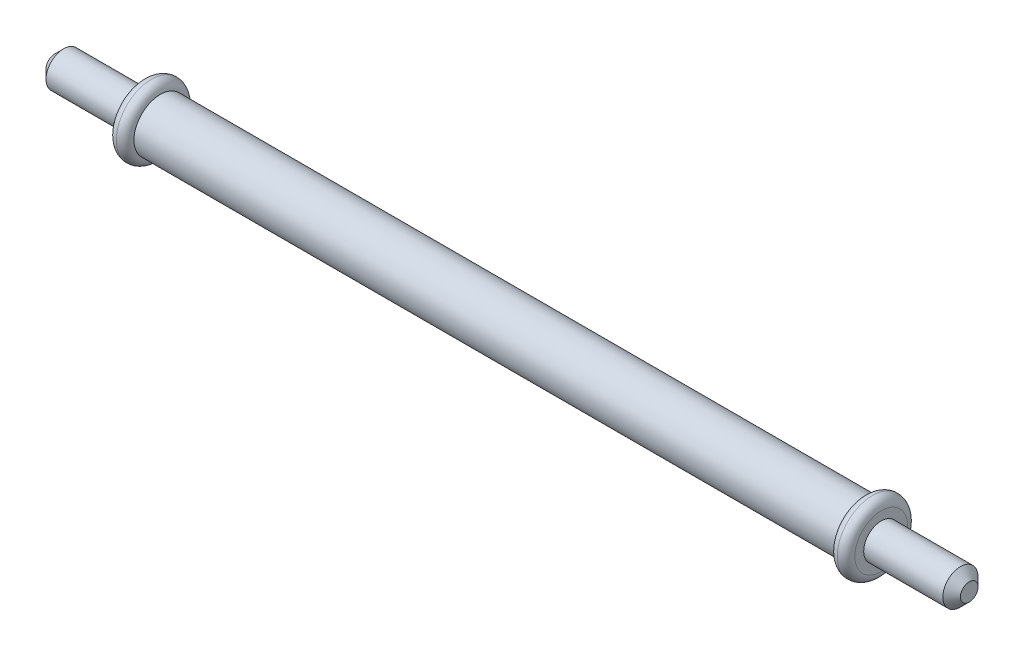
SolidWorks part; units mm, degrees
ref_plane "Front Plane" through (0, 0, 0) normal (0, 0, 1) x (1, 0, 0)
ref_plane "Top Plane" through (0, 0, 0) normal (0, 1, 0) x (1, 0, 0)
ref_plane "Right Plane" through (0, 0, 0) normal (1, 0, 0) x (0, 0, -1)
sketch "Sketch2" plane through (0, 0, 0) normal (0, 0, 1) x (1, 0, 0)
  line L0 (0, 0) -> (114.248, 0) construction
  line L1 (0, 0) -> (104, 0)
  line L2 (0, 0) -> (10, 0)
  line L3 (0, 0) -> (0, 2)
  line L4 (0, 2) -> (10, 2)
  line L5 (10, 0) -> (10, 2)
  line L6 (10, 0) -> (94, 0)
  line L7 (10, 0) -> (10, 3)
  line L8 (10, 3) -> (94, 3)
  line L9 (94, 0) -> (94, 3)
  line L10 (94, 0) -> (104, 0)
  line L11 (94, 0) -> (94, 2)
  line L12 (94, 2) -> (104, 2)
  line L13 (104, 0) -> (104, 2)
  dimension "D1" = 2
  dimension "D2" = 10
  dimension "D3" = 3
  dimension "D4" = 84
  dimension "D5" = 2
  dimension "D6" = 10
revolve "Revolve2" add sketch "Sketch2" angle 360 about L0 region at (5, 1, 0) region at (52, 1.5, 0) region at (99, 1, 0)
sketch "Sketch3" plane through (94, 0, 0) normal (1, 0, 0) x (0, 0, -1)
  circle A0 centre (0, 0) radius 4
  dimension "D1" = 8
extrude "Boss-Extrude1" add sketch "Sketch3" against normal blind 2
fillet "Fillet1" radius 1 2 edges at (94, 0, -4) (92, 0, -4)
chamfer "Chamfer1" distance 1 angle 45 1 edges at (104, 0, 2)
chamfer "Chamfer2" distance 1 angle 45 1 edges at (0, 0, 2)
sketch "Sketch4" plane through (10, 0, 0) normal (-1, 0, 0) x (0, 0, 1)
  circle A0 centre (0, 0) radius 4
  dimension "D1" = 8
extrude "Boss-Extrude2" add sketch "Sketch4" against normal blind 2
fillet "Fillet2" radius 1 2 edges at (10, 0, 4) (12, 0, 4)
